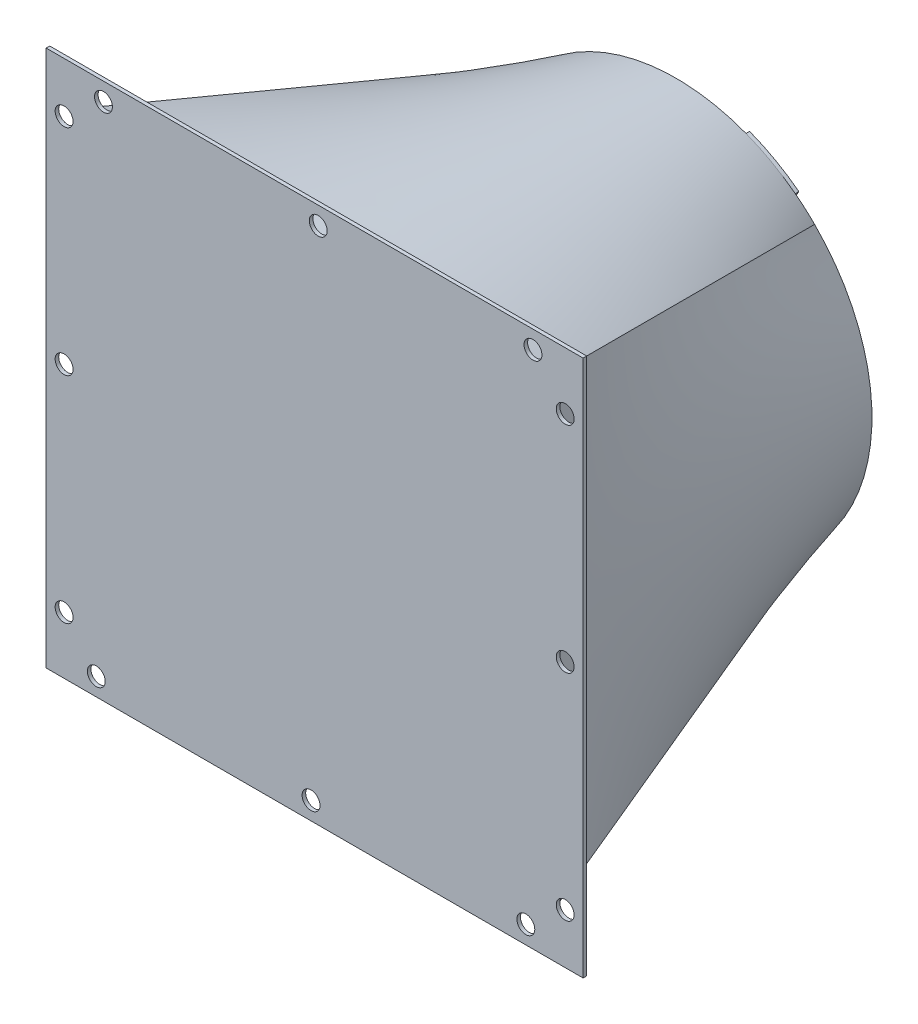
SolidWorks part; units mm, degrees
ref_plane "Piano frontale" through (0, 0, 0) normal (0, 0, 1) x (1, 0, 0)
ref_plane "Piano superiore" through (0, 0, 0) normal (0, 1, 0) x (1, 0, 0)
ref_plane "Piano destro" through (0, 0, 0) normal (1, 0, 0) x (0, 0, -1)
sketch "Schizzo1" plane through (0, 0, 0) normal (0, 0, 1) x (1, 0, 0)
  line L0 (166.3796, -217.1127) -> (131.958, -157.4927) construction
  line L1 (131.958, 157.4927) -> (166.3796, 217.1127) construction
  line L2 (-273.2448, 12.5434) -> (-267.2358, 12.5434) construction
  line L3 (-267.2358, 12.5434) -> (-267.2358, -12.5434) construction
  line L4 (-267.2358, -12.5434) -> (-273.2448, -12.5434) construction
  line L5 (-271.2149, -35.5326) -> (-202.3717, -35.5326) construction
  line L6 (-202.3717, 35.5326) -> (-271.2149, 35.5326) construction
  line L7 (166.3796, -217.1127) -> (131.958, -157.4927)
  line L8 (131.958, 157.4927) -> (166.3796, 217.1127)
  line L9 (-273.2448, 12.5434) -> (-267.2358, 12.5434)
  line L10 (-267.2358, 12.5434) -> (-267.2358, -12.5434)
  line L11 (-267.2358, -12.5434) -> (-273.2448, -12.5434)
  line L12 (-271.2149, -35.5326) -> (-202.3717, -35.5326)
  line L13 (-202.3717, 35.5326) -> (-271.2149, 35.5326)
  arc A0 (97.5976, -255.5284) -> (166.3796, -217.1127) centre (0, 0) ccw construction
  arc A1 (55.4419, -197.8461) -> (131.958, -157.4927) centre (0, 0) ccw construction
  arc A2 (55.4419, -197.8461) -> (97.5976, -255.5284) centre (477.985, 66.714) ccw construction
  arc A3 (131.958, 157.4927) -> (55.4419, 197.8461) centre (0, 0) ccw construction
  arc A4 (166.3796, 217.1127) -> (97.5976, 255.5284) centre (0, 0) ccw construction
  arc A5 (97.5976, 255.5284) -> (55.4419, 197.8461) centre (477.985, -66.714) ccw construction
  arc A6 (-271.2149, 35.5326) -> (-273.2448, 12.5434) centre (0, 0) ccw construction
  arc A7 (-273.2448, -12.5434) -> (-271.2149, -35.5326) centre (0, 0) ccw construction
  arc A8 (-202.3717, 35.5326) -> (-202.3717, -35.5326) centre (0, 0) ccw construction
  arc A9 (97.5976, -255.5284) -> (166.3796, -217.1127) centre (0, 0) ccw
  arc A10 (55.4419, -197.8461) -> (131.958, -157.4927) centre (0, 0) ccw
  arc A11 (55.4419, -197.8461) -> (97.5976, -255.5284) centre (477.985, 66.714) ccw
  arc A12 (131.958, 157.4927) -> (55.4419, 197.8461) centre (0, 0) ccw
  arc A13 (166.3796, 217.1127) -> (97.5976, 255.5284) centre (0, 0) ccw
  arc A14 (97.5976, 255.5284) -> (55.4419, 197.8461) centre (477.985, -66.714) ccw
  arc A15 (-271.2149, 35.5326) -> (-273.2448, 12.5434) centre (0, 0) ccw
  arc A16 (-273.2448, -12.5434) -> (-271.2149, -35.5326) centre (0, 0) ccw
  arc A17 (-202.3717, 35.5326) -> (-202.3717, -35.5326) centre (0, 0) ccw
  arc A18 (125, -225.7564) -> (125, -207.2564) centre (125, -216.5064) ccw construction
  arc A19 (125, -207.2564) -> (125, -225.7564) centre (125, -216.5064) ccw construction
  arc A20 (125, 225.7564) -> (125, 207.2564) centre (125, 216.5064) ccw construction
  arc A21 (125, 207.2564) -> (125, 225.7564) centre (125, 216.5064) ccw construction
  arc A22 (-250, -9.25) -> (-250, 9.25) centre (-250, 0) ccw construction
  arc A23 (-250, 9.25) -> (-250, -9.25) centre (-250, 0) ccw construction
  arc A24 (125, -225.7564) -> (125, -207.2564) centre (125, -216.5064) ccw
  arc A25 (125, -207.2564) -> (125, -225.7564) centre (125, -216.5064) ccw
  arc A26 (125, 225.7564) -> (125, 207.2564) centre (125, 216.5064) ccw
  arc A27 (125, 207.2564) -> (125, 225.7564) centre (125, 216.5064) ccw
  arc A28 (-250, -9.25) -> (-250, 9.25) centre (-250, 0) ccw
  arc A29 (-250, 9.25) -> (-250, -9.25) centre (-250, 0) ccw
extrude "Estrusione-Estrusione1" add sketch "Schizzo1" along normal blind 5
sketch "Schizzo2" plane through (0, 0, 5) normal (0, 0, 1) x (1, 0, 0)
  circle A0 centre (0, 0) radius 273.5326
ref_plane "Piano1" through (0, 0, 505) normal (0, 0, 1) x (1, 0, 0)
sketch "Schizzo3" plane through (0, 0, 505) normal (0, 0, 1) x (1, 0, 0)
  line L1 (325, -325) -> (-325, -325)
  line L2 (325, -325) -> (325, 325)
  line L3 (325, 325) -> (-325, 325)
  line L4 (-325, -325) -> (-325, 325)
  line L5 (325, -325) -> (-325, 325) construction
  line L6 (325, 325) -> (-325, -325) construction
  point P0 (0, 0)
loft "Loft1" add profiles "Schizzo3", "Schizzo2" connector at (325, 325, 505) connector at (273.5326, 0, 5)
sketch "Schizzo4" plane through (0, 0, 505) normal (0, 0, 1) x (1, 0, 0)
  line L1 (375, -375) -> (-375, -375)
  line L2 (375, -375) -> (375, 375)
  line L3 (375, 375) -> (-375, 375)
  line L4 (-375, -375) -> (-375, 375)
  line L5 (375, -375) -> (-375, 375) construction
  line L6 (375, 375) -> (-375, -375) construction
  point P0 (0, 0)
extrude "Estrusione-Estrusione2" add sketch "Schizzo4" along normal blind 5
sketch "Schizzo5" plane through (0, 0, 5) normal (0, 0, -1) x (-1, 0, 0)
  circle A0 centre (-125, -216.5064) radius 9.25 construction
  circle A1 centre (250, 0) radius 9.25 construction
  circle A2 centre (-125, 216.5064) radius 9.25 construction
  circle A3 centre (-125, -216.5064) radius 9.25
  circle A4 centre (250, 0) radius 9.25
  circle A5 centre (-125, 216.5064) radius 9.25
extrude "Taglio-Estrusione1" cut sketch "Schizzo5" against normal blind 100
sketch "Schizzo6" plane through (0, 0, 505) normal (0, 0, -1) x (-1, 0, 0)
  line L0 (-325, 325) -> (325, 325) construction
  circle A0 centre (-305, 350) radius 12.5
  circle A1 centre (-5, 350) radius 12.5
  circle A2 centre (295, 350) radius 12.5
  circle A3 centre (350, 305) radius 12.5
  circle A4 centre (350, 5) radius 12.5
  circle A5 centre (350, -295) radius 12.5
  circle A6 centre (305, -350) radius 12.5
  circle A7 centre (5, -350) radius 12.5
  circle A8 centre (-295, -350) radius 12.5
  circle A9 centre (-350, -305) radius 12.5
  circle A10 centre (-350, -5) radius 12.5
  circle A11 centre (-350, 295) radius 12.5
  point P30 (0, 0)
  dimension "D1" = 25
  dimension "D3" = 25
  dimension "D2" = 20
  dimension "D4" = 3
  dimension "D5" = 4
extrude "Taglio-Estrusione2" cut sketch "Schizzo6" against normal blind 100
